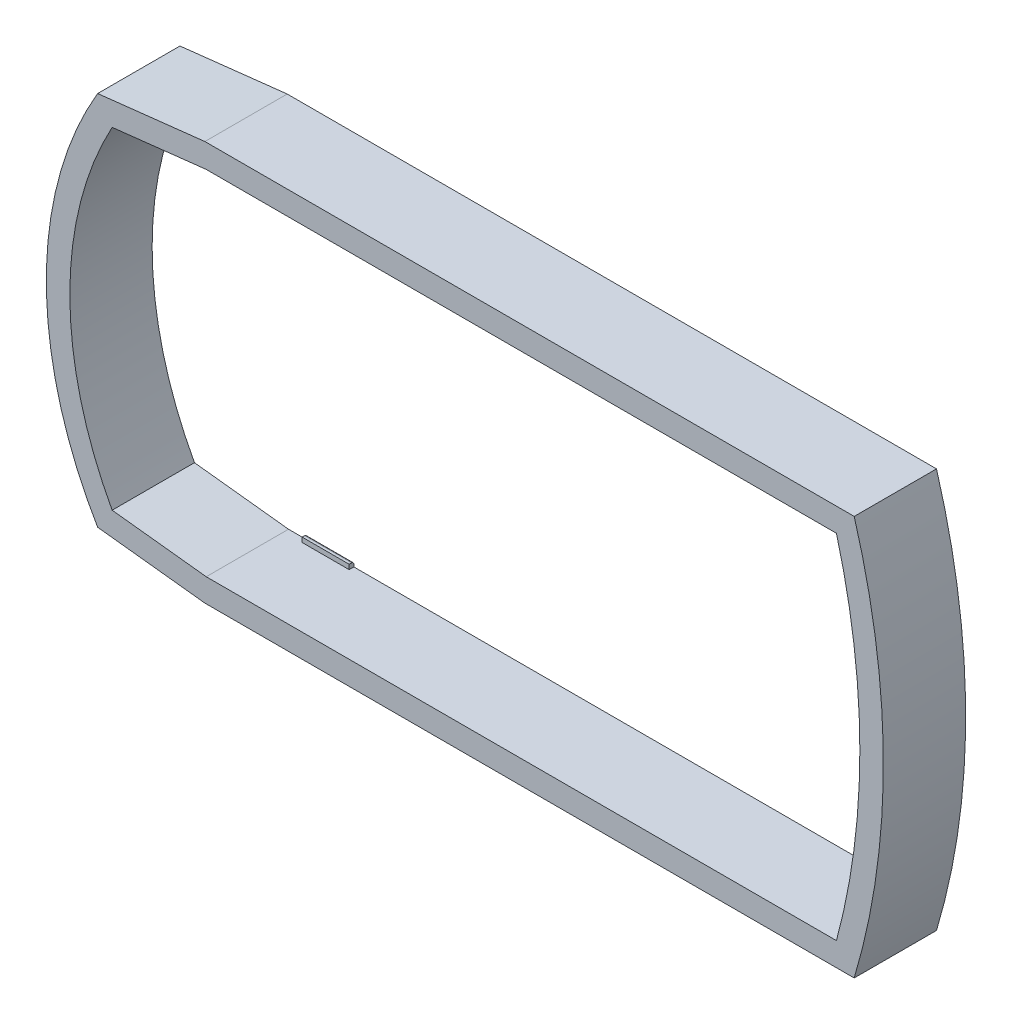
SolidWorks part; units mm, degrees
ref_plane "Plan de face" through (0, 0, 0) normal (0, 0, 1) x (1, 0, 0)
ref_plane "Plan de dessus" through (0, 0, 0) normal (0, 1, 0) x (1, 0, 0)
ref_plane "Plan de droite" through (0, 0, 0) normal (1, 0, 0) x (0, 0, -1)
sketch "Esquisse1" plane through (0, 0, 0) normal (0, 0, 1) x (1, 0, 0)
  line L0 (-192.776, 43.345) -> (-152.776, 47.845)
  line L1 (-152.776, 47.845) -> (115.224, 47.845)
  line L2 (-152.776, 47.845) -> (-152.776, -102.155)
  line L3 (-152.776, -102.155) -> (115.224, -102.155)
  line L4 (115.224, 47.845) -> (115.224, -102.155)
  line L5 (-152.776, 47.845) -> (-192.776, 47.845)
  line L6 (-152.776, 53.8314) -> (-152.776, -102.155)
  line L7 (-152.776, 47.845) -> (-152.776, -102.155)
  line L8 (-152.776, -102.155) -> (-192.776, -102.155)
  line L9 (-192.776, 47.845) -> (-192.776, -102.155)
  line L10 (-152.776, 47.845) -> (-192.776, 47.845)
  line L11 (-152.776, 47.845) -> (-152.776, 43.345)
  line L12 (-152.776, 43.345) -> (-192.776, 43.345)
  line L13 (-192.776, 47.845) -> (-192.776, 43.345)
  line L14 (-152.776, -102.155) -> (-192.776, -102.155)
  line L15 (-152.776, -102.155) -> (-152.776, -97.655)
  line L16 (-152.776, -97.655) -> (-192.776, -97.655)
  line L17 (-192.776, -102.155) -> (-192.776, -97.655)
  line L18 (-192.776, -97.655) -> (-152.776, -102.155)
  line L20 (124.9119, -14.655) -> (121.9119, -14.655)
  line L21 (124.9119, -14.655) -> (124.9119, -39.655)
  line L22 (124.9119, -39.655) -> (121.9119, -39.655)
  line L23 (121.9119, -14.655) -> (121.9119, -39.655)
  line L24 (-144.9874, 47.845) -> (-124.9874, 47.845)
  line L25 (-144.9874, 47.845) -> (-144.9874, 45.845)
  line L26 (-144.9874, 45.845) -> (-124.9874, 45.845)
  line L27 (-124.9874, 47.845) -> (-124.9874, 45.845)
  line L28 (-144.9874, -102.155) -> (-124.9874, -102.155)
  line L29 (-144.9874, -102.155) -> (-144.9874, -100.155)
  line L30 (-144.9874, -100.155) -> (-124.9874, -100.155)
  line L31 (-124.9874, -102.155) -> (-124.9874, -100.155)
  arc A0 (115.224, -102.155) -> (115.224, 47.845) centre (-162.1791, -27.155) ccw
  arc A1 (-192.776, -97.655) -> (-192.776, 43.345) centre (-63.7022, -27.155) cw
  point P11 (-210.776, -27.155)
  point P12 (125.224, -27.155)
  dimension "D10" = 12.5
  dimension "D1" = 268
  dimension "D2" = 150
  dimension "D3" = 40
  dimension "D4" = 4.5
  dimension "D5" = 4.5
  dimension "D6" = 18
  dimension "D7" = 75
  dimension "D8" = 10
  dimension "D9" = 75
  dimension "D11" = 12.5
  dimension "D12" = 3
  dimension "D13" = 48
  dimension "D14" = 2
  dimension "D15" = 20
  dimension "D16" = 20
  dimension "D17" = 2
  dimension "D18" = 48
extrude "Extru.-Mince1" add sketch "Esquisse1" along normal blind 35 thin contours L3 A0 L1 L0 A1 L18 thin type one direction wall 10
extrude "Boss.-Extru.1" add sketch "Esquisse1<13>" along normal blind 2 separate body contours L20 L23 L22 L21 region at (123.4119, -27.155, 0)
sketch "Esquisse1<13>" plane through (0, 0, 0) normal (0, 0, 1) x (1, 0, 0) same geometry as "Esquisse1"
extrude "Boss.-Extru.2" add sketch "Esquisse1<14>" along normal blind 2 contours L3 L31 L30 L29 region at (-134.9874, -101.155, 0)
sketch "Esquisse1<14>" plane through (0, 0, 0) normal (0, 0, 1) x (1, 0, 0) same geometry as "Esquisse1"
extrude "Boss.-Extru.3" add sketch "Esquisse1<15>" along normal blind 2 contours L27 L1 L25 L26 region at (-134.9874, 46.845, 0)
sketch "Esquisse1<15>" plane through (0, 0, 0) normal (0, 0, 1) x (1, 0, 0) same geometry as "Esquisse1"
fillet "Congé2" radius 1 1 edges at (-134.9874, 45.845, 0)
fillet "Congé3" radius 1 1 edges at (-134.9874, -100.155, 0)
fillet "Congé4" radius 0.5 1 edges at (121.9119, -27.155, 0)
